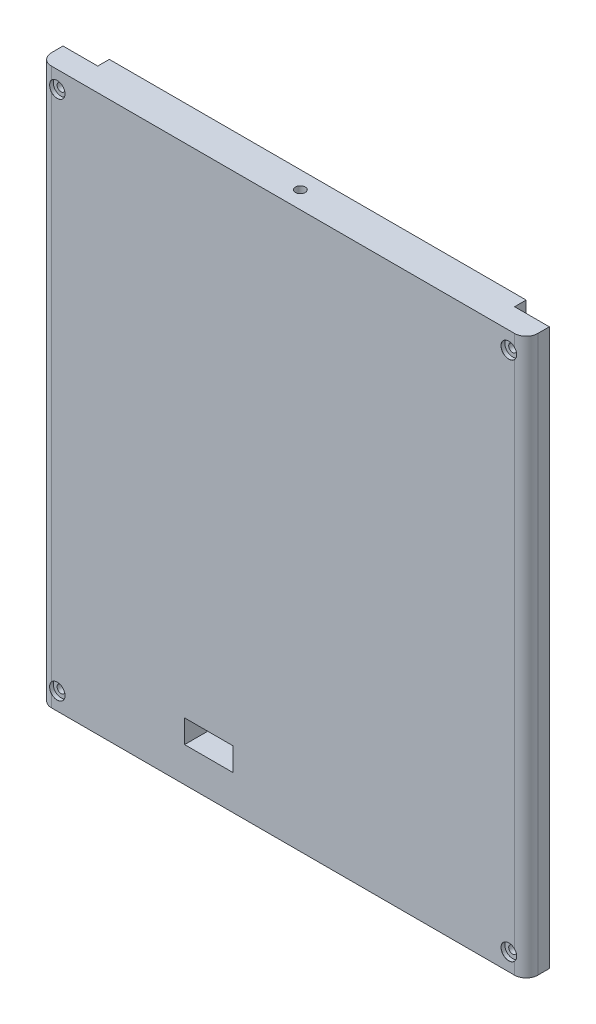
SolidWorks part; units mm, degrees
ref_plane "Front Plane" through (0, 0, 0) normal (0, 0, 1) x (1, 0, 0)
ref_plane "Top Plane" through (0, 0, 0) normal (0, 1, 0) x (1, 0, 0)
ref_plane "Right Plane" through (0, 0, 0) normal (1, 0, 0) x (0, 0, -1)
sketch "Sketch3" plane through (0, 0, 0) normal (0, 1, 0) x (1, 0, 0)
  line L0 (-105, 0) -> (105, 0)
  line L1 (105, 0) -> (105, -10)
  line L2 (105, -10) -> (-105, -10)
  line L3 (-105, -10) -> (-105, 0)
  dimension "D1" = 210
  dimension "D2" = 10
extrude "Boss-Extrude1" add sketch "Sketch3" along normal blind 240
ref_plane "Plane1" through (0, 35, 0) normal (0, 1, 0) x (1, 0, 0)
sketch "Sketch5" plane through (0, 240, 0) normal (0, 1, 0) x (1, 0, 0)
  line L0 (-90, 0) -> (-90, 5)
  line L1 (105, 0) -> (-105, 0) construction
  line L2 (-90, 5) -> (90, 5)
  line L3 (90, 5) -> (90, 0)
  line L4 (-105, 0) -> (-105, -10) construction
  line L5 (105, 0) -> (90, 0)
  line L9 (-105, 0) -> (-105, -10)
  line L10 (-105, -10) -> (105, -10)
  line L11 (105, -10) -> (105, 0)
  line L12 (105, 0) -> (-105, 0)
  line L13 (-105, 0) -> (-105, -10)
  line L14 (-105, -10) -> (105, -10)
  line L15 (105, -10) -> (105, 0)
  line L16 (-90, 0) -> (-105, 0)
  dimension "D1" = 180
  dimension "D2" = 5
  dimension "D3" = 15
  dimension "D4" = 0
extrude "Boss-Extrude2" add sketch "Sketch5" against normal up to surface (205 mm away) up to plane "Plane1"
sketch "Sketch6" plane through (0, 35, 0) normal (0, 1, 0) x (1, 0, 0)
  line L0 (-22.5, 0) -> (-22.5, 15)
  line L2 (-22.5, 15) -> (22.5, 15)
  line L3 (22.5, 15) -> (22.5, 0)
  line L4 (22.5, 0) -> (-22.5, 0)
  line L6 (90, 5) -> (-90, 5) construction
  dimension "D1" = 45
  dimension "D2" = 10
extrude "Boss-Extrude3" add sketch "Sketch6" against normal blind 10
sketch "Sketch7" plane through (0, 0, 10) normal (0, 0, 1) x (1, 0, 0)
  line L0 (0, -1000) -> (0, 49000) construction
  line L1 (-105, 240) -> (105, 240) construction
  line L2 (-105, 240) -> (-105, 0) construction
  line L3 (8.25, 0) -> (-8.25, 0) construction
  circle A0 centre (-97.5, 232.5) radius 1.65
  circle A1 centre (-97.5, 7.5) radius 1.65
  circle A2 centre (97.5, 7.5) radius 1.65
  circle A3 centre (97.5, 232.5) radius 1.65
  dimension "D1" = 3.3
  dimension "D2" = 7.5
  dimension "D4" = 7.5
  dimension "D3" = 7.5
  dimension "D5" = 7.5
extrude "Cut-Extrude1" cut sketch "Sketch7" against normal up to surface (10 mm away) up to face at (0, 95.8333, 0)
sketch "Sketch8" plane through (0, 0, 10) normal (0, 0, 1) x (1, 0, 0)
  line L0 (-105, 240) -> (-105, 0) construction
  line L1 (-42.5, 25) -> (-21.5, 25)
  line L2 (-42.5, 25) -> (-42.5, 15)
  line L3 (-42.5, 15) -> (-21.5, 15)
  line L4 (-21.5, 25) -> (-21.5, 15)
  line L5 (-105, 0) -> (105, 0) construction
  line L6 (0, -1000) -> (0, 49000) construction
  line L7 (42.5, 15) -> (21.5, 15)
  line L8 (21.5, 25) -> (21.5, 15)
  line L9 (42.5, 25) -> (21.5, 25)
  line L10 (42.5, 25) -> (42.5, 15)
  dimension "D1" = 62.5
  dimension "D2" = 15
  dimension "D3" = 21
  dimension "D4" = 10
extrude "Cut-Extrude2" cut sketch "Sketch8" against normal up to surface (10 mm away) contours L4 L1 L2 L3 up to face at (99.15, 232.5, 0)
sketch "Sketch10" plane through (0, 240, 0) normal (0, 1, 0) x (1, 0, 0)
  line L0 (-105, -10) -> (105, -10) construction
  circle A0 centre (0, -2.5) radius 2.1
  dimension "D1" = 4.2
  dimension "D2" = 7.5
extrude "Cut-Extrude3" cut sketch "Sketch10" against normal blind 4.5
sketch "Sketch9" plane through (0, 0, 0) normal (0, -1, 0) x (1, 0, 0)
  line L4 (-105, 10) -> (-105, 0)
  line L5 (-105, 0) -> (105, 0)
  line L6 (105, 0) -> (105, 10)
  line L7 (105, 10) -> (-105, 10)
  line L8 (-105, 10) -> (-105, 0)
  line L9 (-105, 0) -> (105, 0)
  line L10 (105, 0) -> (105, 10)
  line L11 (105, 10) -> (-105, 10)
  dimension "D1" = 0
extrude "Boss-Extrude4" [suppressed] add sketch "Sketch9" along normal blind 40
hole_wizard "CBORE for M3 SBHCS1" positions "3DSketch1" profile "Sketch11" counterbore size "M3" standard "ANSI Metric"
sketch3d "3DSketch1"
  line L0 (-97.5, 232.5, 0) -> (-97.5, 232.5, 10) construction
  circle A0 centre (-97.5, 232.5, 10) radius 1.65 construction
  circle A1 centre (97.5, 232.5, 10) radius 1.65 construction
  point P0 (-96.752, 231.0293, 10)
  point P4 (-97.5, 232.5, 11.65)
  point P5 (-97.5, 232.5, 10)
  point P9 (99.1302, 232.2454, 10)
  point P13 (97.5, 232.5, 11.65)
sketch "Sketch11" plane through (-97.5, 232.5, 10) normal (1, 0, 0) x (0, -1, 0)
  line L0 (0, 0) -> (0, 25)
  line L1 (0, 25) -> (1.7, 25)
  line L3 (1.7, 25) -> (1.7, 1.65)
  line L4 (3.35, 1.65) -> (1.7, 1.65)
  line L5 (3.35, 1.65) -> (3.35, 0.025)
  line L6 (3.35, 0.025) -> (3.375, 0)
  line L7 (3.375, 0) -> (0, 0)
  line L8 (-3.35, 0.025) -> (-3.375, 0) construction
  line L11 (0, -6.35) -> (0, 107.95) construction
  dimension "Thru Hole Dia." = 3.4
  dimension "Thru Hole Depth" = 25
  dimension "C'Bore Dia." = 6.7
  dimension "C'Bore Depth" = 1.65
  dimension "Near C'Sink Dia." = 6.75
  dimension "Near C'Sink Angle" = 90
hole_wizard "CBORE for M3 SBHCS2" positions "3DSketch2" profile "Sketch12" counterbore size "M3" standard "ANSI Metric" end condition through all
sketch3d "3DSketch2"
  line L0 (97.5, 232.5, 0) -> (97.5, 232.5, 10) construction
  point P0 (97.5, 232.5, 10)
sketch "Sketch12" plane through (97.5, 232.5, 10) normal (1, 0, 0) x (0, -1, 0)
  line L0 (0, 0) -> (0, 25)
  line L1 (0, 25) -> (1.7, 25)
  line L3 (1.7, 25) -> (1.7, 1.65)
  line L4 (3.35, 1.65) -> (1.7, 1.65)
  line L5 (3.35, 1.65) -> (3.35, 0.025)
  line L6 (3.35, 0.025) -> (3.375, 0)
  line L7 (3.375, 0) -> (0, 0)
  line L8 (-3.35, 0.025) -> (-3.375, 0) construction
  line L11 (0, -6.35) -> (0, 107.95) construction
  dimension "Thru Hole Dia." = 3.4
  dimension "Thru Hole Depth" = 25
  dimension "C'Bore Dia." = 6.7
  dimension "C'Bore Depth" = 1.65
  dimension "Near C'Sink Dia." = 6.75
  dimension "Near C'Sink Angle" = 90
hole_wizard "CBORE for M3 SBHCS4" positions "3DSketch4" profile "Sketch14" counterbore size "M3" standard "ANSI Metric"
sketch3d "3DSketch4"
  line L0 (97.5, 7.5, 0) -> (97.5, 7.5, 10) construction
  circle A0 centre (97.5, 7.5, 10) radius 1.65 construction
  point P0 (98.8953, 6.6193, 10)
  point P4 (97.5, 7.5, 11.65)
  point P5 (97.5, 7.5, 10)
sketch "Sketch14" plane through (97.5, 7.5, 10) normal (1, 0, 0) x (0, -1, 0)
  line L0 (0, 0) -> (0, 25)
  line L1 (0, 25) -> (1.7, 25)
  line L3 (1.7, 25) -> (1.7, 1.65)
  line L4 (3.35, 1.65) -> (1.7, 1.65)
  line L5 (3.35, 1.65) -> (3.35, 0.025)
  line L6 (3.35, 0.025) -> (3.375, 0)
  line L7 (3.375, 0) -> (0, 0)
  line L8 (-3.35, 0.025) -> (-3.375, 0) construction
  line L11 (0, -6.35) -> (0, 107.95) construction
  dimension "Thru Hole Dia." = 3.4
  dimension "Thru Hole Depth" = 25
  dimension "C'Bore Dia." = 6.7
  dimension "C'Bore Depth" = 1.65
  dimension "Near C'Sink Dia." = 6.75
  dimension "Near C'Sink Angle" = 90
hole_wizard "CBORE for M3 SBHCS5" positions "3DSketch8" profile "Sketch18" counterbore size "M3" standard "ANSI Metric" end condition through all
sketch3d "3DSketch8"
  line L0 (-97.5, 7.5, 0) -> (-97.5, 7.5, 10) construction
  point P0 (-97.5, 7.5, 10)
sketch "Sketch18" plane through (-97.5, 7.5, 10) normal (1, 0, 0) x (0, -1, 0)
  line L0 (0, 0) -> (0, 25)
  line L1 (0, 25) -> (1.7, 25)
  line L3 (1.7, 25) -> (1.7, 1.65)
  line L4 (3.35, 1.65) -> (1.7, 1.65)
  line L5 (3.35, 1.65) -> (3.35, 0.025)
  line L6 (3.35, 0.025) -> (3.375, 0)
  line L7 (3.375, 0) -> (0, 0)
  line L8 (-3.35, 0.025) -> (-3.375, 0) construction
  line L11 (0, -6.35) -> (0, 107.95) construction
  dimension "Thru Hole Dia." = 3.4
  dimension "Thru Hole Depth" = 25
  dimension "C'Bore Dia." = 6.7
  dimension "C'Bore Depth" = 1.65
  dimension "Near C'Sink Dia." = 6.75
  dimension "Near C'Sink Angle" = 90
fillet "Fillet2" radius 5 2 edges at (105, 120, 10) (-105, 120, 10)
